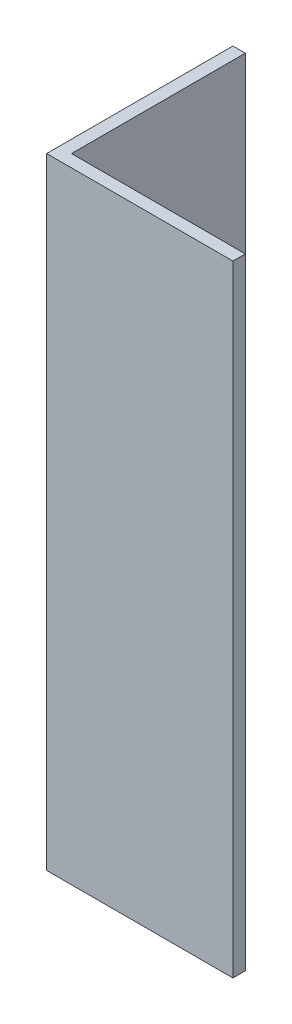
SolidWorks part; units mm, degrees
material "1060 Сплав"
ref_plane "Спереди" through (0, 0, 0) normal (0, 0, 1) x (1, 0, 0)
ref_plane "Сверху" through (0, 0, 0) normal (0, 1, 0) x (1, 0, 0)
ref_plane "Справа" through (0, 0, 0) normal (1, 0, 0) x (0, 0, -1)
sketch "Эскиз1" plane through (0, 0, 0) normal (0, 1, 0) x (1, 0, 0)
  line L0 (0, 0) -> (0, 15)
  line L1 (0, 15) -> (1, 15)
  line L2 (1, 15) -> (1, 1)
  line L3 (1, 1) -> (15, 1)
  line L4 (15, 1) -> (15, 0)
  line L5 (15, 0) -> (0, 0)
  dimension "D1" = 1
  dimension "D2" = 15
extrude "Бобышка-Вытянуть1" add sketch "Эскиз1" along normal blind 50
sketch "Эскиз2" plane through (1, 0, 0) normal (1, 0, 0) x (0, 0, -1)
  circle A0 centre (10.5, 9.5) radius 2.25 construction
  circle A1 centre (10.5, 9.5) radius 2.25
  circle A2 centre (10.5, 160.5) radius 2.25 construction
  circle A3 centre (10.5, 160.5) radius 2.25
extrude "Вырез-Вытянуть1" cut sketch "Эскиз2" against normal through all
